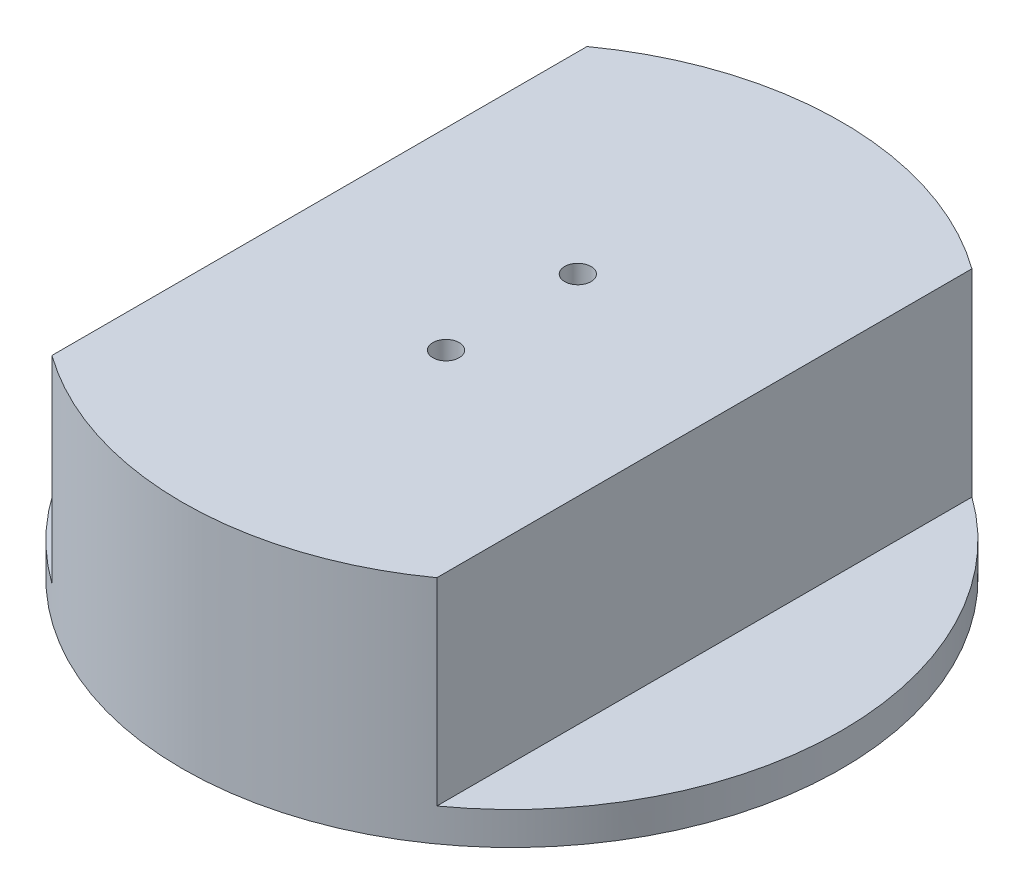
SolidWorks part; units mm, degrees
ref_plane "Ön Düzlem" through (0, 0, 0) normal (0, 0, 1) x (1, 0, 0)
ref_plane "Üst Düzlem" through (0, 0, 0) normal (0, 1, 0) x (1, 0, 0)
ref_plane "Sağ Düzlem" through (0, 0, 0) normal (1, 0, 0) x (0, 0, -1)
sketch "Çizim1" plane through (0, 0, 0) normal (0, 1, 0) x (1, 0, 0)
  line L0 (0, 0) -> (0, 50) construction
  line L1 (-29.199, 40.5884) -> (-29.199, -40.5884)
  line L2 (-47.199, 16.5) -> (-29.199, 16.5)
  line L3 (-47.199, 16.5) -> (-47.199, -16.5)
  line L4 (-47.199, -16.5) -> (-29.199, -16.5)
  line L5 (-29.199, 16.5) -> (-29.199, -16.5)
  line L6 (29.199, 40.5884) -> (29.199, -40.5884)
  line L7 (47.199, -16.5) -> (29.199, -16.5)
  line L8 (29.199, 16.5) -> (29.199, -16.5)
  line L9 (47.199, 16.5) -> (29.199, 16.5)
  line L10 (47.199, 16.5) -> (47.199, -16.5)
  circle A0 centre (0, 0) radius 50
  point P8 (-29.199, 0)
  dimension "D1" = 100
  dimension "D2" = 18
  dimension "D3" = 33
extrude "base" add sketch "Çizim1" against normal blind 5 contours L1 A0 L2 | L3 A0 | L3 L4 L1 L2 | L4 A0 L1 | L6 A0 L1 | L6 A0 L7 | L10 L9 L6 L7 | L9 A0 L6 | L10 A0 region at (0, 0, 0) region at (-35.8614, 0, -25.3381) region at (-38.199, 0, 0) region at (35.8614, 0, -25.3381) region at (-48.3222, 0, 0) region at (-35.8614, 0, 25.3381) region at (38.199, 0, 0) region at (48.3222, 0, 0) region at (35.8614, 0, 25.3381)
extrude "Yükseklik-Ekstrüzyon2" add sketch "Çizim1<3>" along normal blind 30 contours L6 A0 L1 region at (0, 0, 0)
sketch "Çizim1<3>" plane through (0, 0, 0) normal (0, 1, 0) x (1, 0, 0) same geometry as "Çizim1"
sketch "Çizim2" plane through (0, 30, 0) normal (0, 1, 0) x (1, 0, 0)
  line L0 (0, 0) -> (29.199, 0) construction
  line L1 (29.199, 40.5884) -> (29.199, -40.5884) construction
  circle A1 centre (0, 10) radius 2
  circle A2 centre (0, -10) radius 2
  point P7 (-7.3115, 6.8222)
  dimension "D1" = 4
  dimension "D2" = 10
extrude "banana slotu" cut sketch "Çizim2" against normal through all
